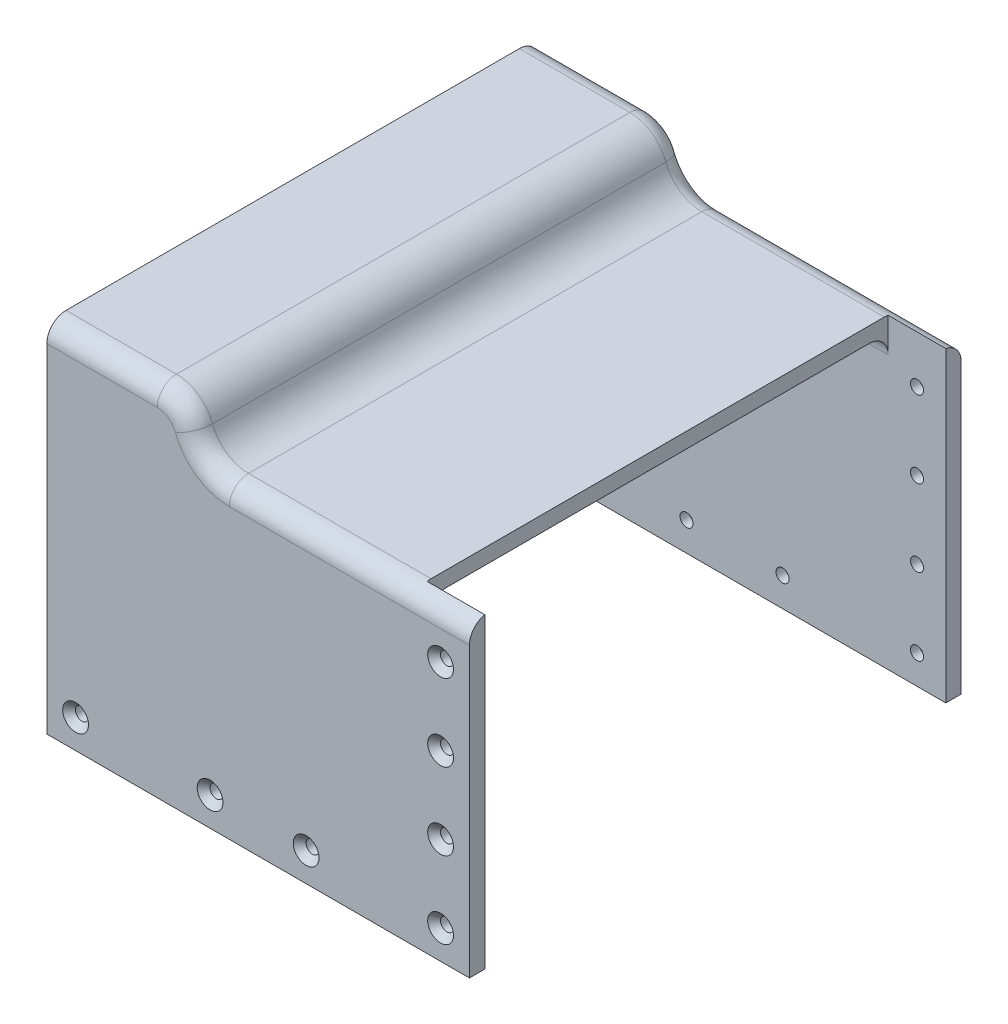
SolidWorks part; units mm, degrees
ref_plane "Front Plane" through (0, 0, 0) normal (0, 0, 1) x (1, 0, 0)
ref_plane "Top Plane" through (0, 0, 0) normal (0, 1, 0) x (1, 0, 0)
ref_plane "Right Plane" through (0, 0, 0) normal (1, 0, 0) x (0, 0, -1)
ref_axis "X" through (88.99, 0, 0) along (-1, 0, 0)
ref_axis "Y" through (0, 55, 0) along (0, -1, 0)
ref_axis "Z" through (0, 0, -88.99) along (0, 0, 1)
sketch "Sketch1" plane through (0, 0, 0) normal (0, 0, 1) x (1, 0, 0)
  line L1 (-47.5, -32.5) -> (47.5, -32.5)
  line L2 (-47.5, -32.5) -> (-47.5, 32.5)
  line L3 (-10, 32.5) -> (47.5, 32.5)
  line L4 (47.5, -32.5) -> (47.5, 32.5)
  line L5 (-47.5, -32.5) -> (47.5, 32.5) construction
  line L6 (-47.5, 32.5) -> (47.5, -32.5) construction
  line L8 (-47.5, 32.5) -> (-47.5, 45.5)
  line L9 (-47.5, 45.5) -> (-10, 45.5)
  line L10 (-10, 32.5) -> (-10, 45.5)
  point P0 (0, 0)
  dimension "D1" = 65
  dimension "D2" = 95
  dimension "D3" = 13
  dimension "D4" = 10
extrude "Boss-Extrude1" add sketch "Sketch1" along normal mid plane 128
shell "Shell1" thickness 4 removed face at (47.5, 0, 0) removed face at (-47.5, 6.5, 0) removed face at (0, -32.5, 0)
fillet "Fillet1" radius 10 1 edges at (-10, 32.5, 0)
fillet "Fillet2" radius 10 1 edges at (-10, 45.5, 0)
fillet "Fillet4" radius 10 1 edges at (-14, 28.5, 0)
fillet "Fillet6" radius 10 1 edges at (-14, 41.5, 0)
sketch "Sketch3" plane through (0, -32.5, 0) normal (0, -1, 0) x (1, 0, 0)
  line L1 (47.5, 64) -> (-47.5, 64)
  line L2 (47.5, 64) -> (47.5, 60)
  line L3 (47.5, 60) -> (-47.5, 60)
  line L4 (-47.5, 64) -> (-47.5, 60)
  line L5 (-47.5, -60) -> (47.5, -60)
  line L6 (-47.5, -60) -> (-47.5, -64)
  line L7 (-47.5, -64) -> (47.5, -64)
  line L8 (47.5, -60) -> (47.5, -64)
extrude "Boss-Extrude4" add sketch "Sketch3" along normal blind 15
sketch "Sketch4" plane through (47.5, 0, 0) normal (-1, 0, 0) x (0, 0, 1)
  line L1 (64, -47.5) -> (60, -47.5)
  line L2 (64, -47.5) -> (64, 32.5)
  line L3 (64, 32.5) -> (60, 32.5)
  line L4 (60, -47.5) -> (60, 32.5)
  line L5 (-60, 41.5) -> (-60, -47.5) construction
  line L6 (-64, -47.5) -> (-60, -47.5)
  line L7 (-64, -47.5) -> (-64, 32.5)
  line L8 (-64, 32.5) -> (-60, 32.5)
  line L9 (-60, -47.5) -> (-60, 32.5)
  line L10 (60, 41.5) -> (60, -47.5) construction
  line L11 (64, 32.5) -> (-64, 32.5) construction
extrude "Boss-Extrude5" add sketch "Sketch4" against normal blind 15
fillet "Fillet7" radius 5 8 edges at (21.75, 28.5, 60) (-9.7009, 30.2842, 60) (21.75, 28.5, -60) (-9.7009, 30.2842, -60) (-35.1175, 41.5, 60) (-35.1175, 41.5, -60) (-17.0341, 39.7158, 60) (-17.0341, 39.7158, -60)
fillet "Fillet8" radius 5 8 edges at (-33.1175, 45.5, -64) (-5.7009, 34.2842, -64) (-33.1175, 45.5, 64) (-5.7009, 34.2842, 64) (31.25, 32.5, -64) (31.25, 32.5, 64) (-13.0341, 43.7158, -64) (-13.0341, 43.7158, 64)
sketch "Sketch5" plane through (0, 0, -64) normal (0, 0, -1) x (-1, 0, 0)
  line L0 (47.5, 40.5) -> (47.5, -47.5) construction
  line L1 (47.5, -47.5) -> (-62.5, -47.5) construction
  line L2 (-62.5, 27.5) -> (-62.5, -47.5) construction
  line L3 (0, 27.5) -> (-62.5, 27.5) construction
  point P0 (-55, -40)
  point P1 (40, -40)
  point P2 (5, -40)
  point P3 (-20, -40)
  point P4 (-55, -20)
  point P5 (-55, 0)
  point P6 (-55, 20)
  dimension "D1" = 7.5
  dimension "D2" = 7.5
  dimension "D3" = 7.5
  dimension "D4" = 35
  dimension "D5" = 35
  dimension "D6" = 7.5
  dimension "D7" = 20
  dimension "D8" = 20
hole_wizard "CSK for M3 SFHCS1" positions "3DSketch1" profile "Sketch6" countersink size "M3" standard "ANSI Metric"
sketch3d "3DSketch1"
  point P0 (-40, -40, -64)
  point P3 (-5, -40, -64)
  point P6 (20, -40, -64)
  point P9 (55, -40, -64)
  point P12 (55, -20, -64)
  point P15 (55, 0, -64)
  point P18 (55, 20, -64)
sketch "Sketch6" plane through (-40, -40, -64) normal (1, 0, 0) x (0, 1, 0)
  line L0 (0, 0) -> (0, 16.0215)
  line L1 (0, 16.0215) -> (1.7, 15)
  line L2 (1.7, 15) -> (1.7, 1.66)
  line L3 (1.7, 1.66) -> (3.36, 0)
  line L5 (3.36, 0) -> (0, 0)
  line L6 (-1.7, 1.66) -> (-3.36, 0) construction
  line L10 (0, 16.0215) -> (-1.7, 15) construction
  line L11 (0, -6.35) -> (0, 107.95) construction
  dimension "Hole Dia." = 3.4
  dimension "Hole Depth" = 15
  dimension "Near C'Sink Dia." = 6.72
  dimension "Near C'Sink Angle" = 90
  dimension "Drill Angle" = 118
mirror "Mirror1" about plane through (0, 0, 0) normal (0, 0, 1) of "CSK for M3 SFHCS1"
